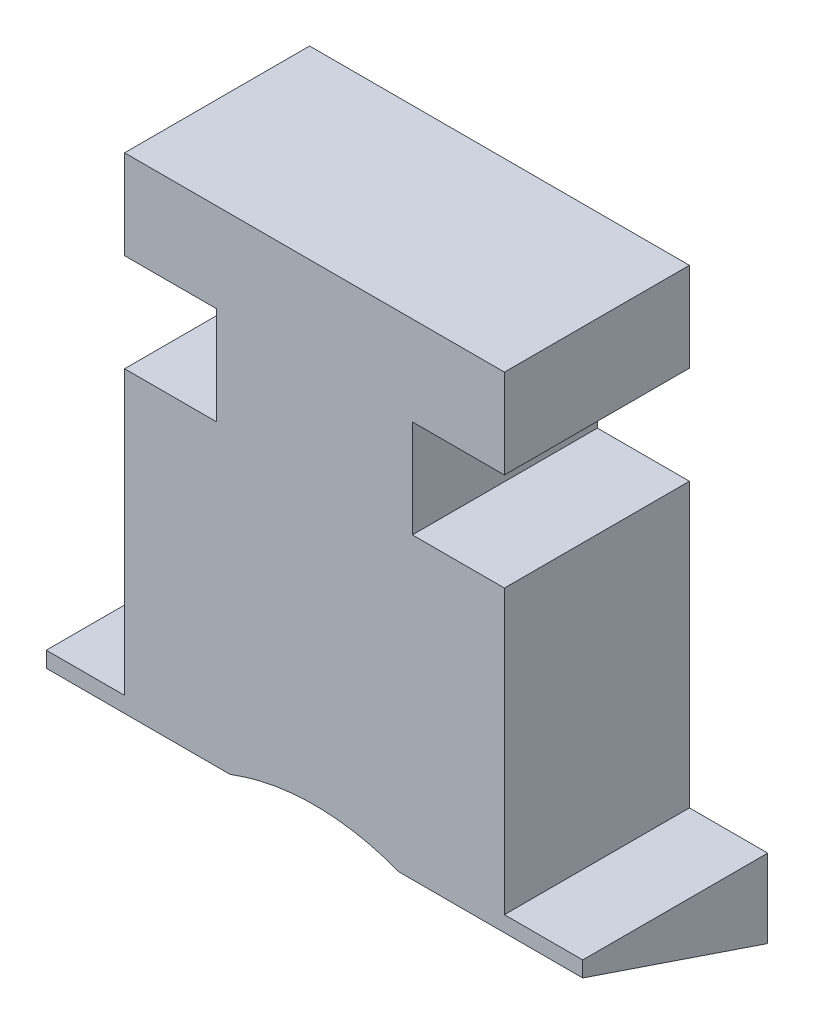
SolidWorks part; units mm, degrees
ref_plane "Front Plane" through (0, 0, 0) normal (0, 0, 1) x (1, 0, 0)
ref_plane "Top Plane" through (0, 0, 0) normal (0, 1, 0) x (1, 0, 0)
ref_plane "Right Plane" through (0, 0, 0) normal (1, 0, 0) x (0, 0, -1)
sketch "Sketch1" plane through (0, 0, 0) normal (0, 1, 0) x (1, 0, 0)
  line L0 (-8.6995, 5.54) -> (8.6995, 5.54)
  line L1 (-6.1595, 3) -> (6.1595, 3)
  line L2 (-6.1595, 3) -> (-6.1595, -3)
  line L3 (-6.1595, -3) -> (6.1595, -3)
  line L4 (6.1595, 3) -> (6.1595, -3)
  line L5 (8.6995, 5.54) -> (8.6995, -5.54)
  line L6 (-8.6995, -5.54) -> (8.6995, -5.54)
  line L7 (-8.6995, 5.54) -> (-8.6995, -5.54)
  line L8 (-8.6995, 3) -> (8.6995, 3)
  line L9 (-8.6995, -3) -> (8.6995, -3)
  point P4 (0, 3)
  point P6 (-6.1595, 0)
  dimension "D1" = 6
  dimension "D2" = 12.319
  dimension "D3" = 2.54
extrude "Boss-Extrude1" add sketch "Sketch1" along normal blind 15.24 contours L4 L1 L2 L3 region at (0, 0, 0)
extrude "Boss-Extrude2" add sketch "Sketch1<3>" against normal blind 2.54 contours L4 L1 L2 L3 | L4 L9 L5 L8 | L7 L9 L2 L8 region at (-7.4295, 0, 0) region at (7.4295, 0, 0) region at (0, 0, 0)
sketch "Sketch1<3>" plane through (0, 0, 0) normal (0, 1, 0) x (1, 0, 0) same geometry as "Sketch1"
sketch "Sketch2" plane through (0, 0, -3) normal (0, 0, -1) x (-1, 0, 0)
  line L0 (-6.1595, 15.24) -> (-6.1595, 0) construction
  line L1 (-6.1595, 12.35) -> (6.1595, 12.35)
  line L2 (-6.1595, 12.35) -> (-6.1595, 9.175)
  line L3 (-6.1595, 9.175) -> (6.1595, 9.175)
  line L4 (6.1595, 12.35) -> (6.1595, 9.175)
  line L5 (6.1595, 15.24) -> (6.1595, 0) construction
  line L6 (-3.175, 12.35) -> (3.175, 12.35)
  line L7 (-3.175, 12.35) -> (-3.175, 9.175)
  line L8 (-3.175, 9.175) -> (3.175, 9.175)
  line L9 (3.175, 12.35) -> (3.175, 9.175)
  line L10 (-6.1595, 0) -> (-8.6995, 0) construction
  line L11 (-3.175, 12.35) -> (3.175, 12.35)
  line L12 (-3.175, 12.35) -> (3.175, 9.175) construction
  line L13 (3.175, 12.35) -> (-3.175, 9.175) construction
  point P14 (0, 10.7625)
  line M11 (-6.1595, 15.24) -> (-6.1595, 0)
  line M17 (6.1595, 0) -> (6.1595, 15.24)
  dimension "D1" = 9.175
  dimension "D2" = 3.175
  dimension "D3" = 6.35
extrude "Cut-Extrude1" cut sketch "Sketch2" against normal through all contours L7 L1 L3 M11 | L1 L9 L3 M17 region at (4.6672, 10.7625, -3) region at (-4.6673, 10.7625, -3)
sketch "Sketch3" plane through (-8.6995, 0, 0) normal (-1, 0, 0) x (0, 0, 1)
  line L0 (-3, -2.54) -> (3, -0.508)
  line L1 (3, -2.54) -> (3, 0) construction
  line L2 (3, -0.508) -> (3, -2.54)
  line L3 (-3, -2.54) -> (3, -2.54) construction
  line L4 (3, -2.54) -> (-3, -2.54)
  dimension "D1" = 2.032
extrude "Cut-Extrude2" cut sketch "Sketch3" against normal through all
sketch "Sketch4" plane through (0, 0, 3) normal (0, 0, 1) x (1, 0, 0)
  line L0 (-6.1595, 0) -> (6.1595, 0) construction
  circle A0 centre (0, -7.62) radius 7.62
  dimension "D1" = 15.24
extrude "Cut-Extrude3" cut sketch "Sketch4" against normal blind 3.175
